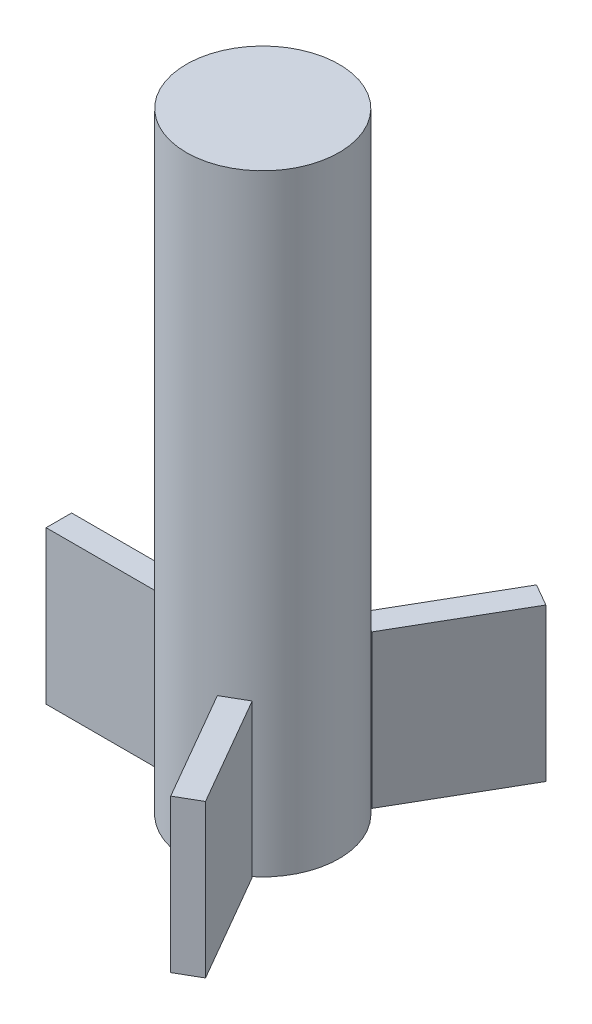
SolidWorks part; units mm, degrees
ref_plane "Alzado" through (0, 0, 0) normal (0, 0, 1) x (1, 0, 0)
ref_plane "Planta" through (0, 0, 0) normal (0, 1, 0) x (1, 0, 0)
ref_plane "Vista lateral" through (0, 0, 0) normal (1, 0, 0) x (0, 0, -1)
sketch "Croquis3" plane through (0, 0, 0) normal (0, 1, 0) x (1, 0, 0)
  line L0 (0, 0.7) -> (0, 13618.4959) construction
  line L1 (-0.6667, 0) -> (-15, 0) construction
  line L2 (-15, 2.5) -> (-40, 2.5)
  line L4 (-15, 2.5) -> (-15, -2.5)
  line L5 (-15, -2.5) -> (-40, -2.5)
  line L6 (-40, 2.5) -> (-40, -2.5)
  line L7 (9.6651, 11.7404) -> (22.1651, 33.391)
  line L8 (22.1651, 33.391) -> (17.8349, 35.891)
  line L9 (5.3349, 14.2404) -> (17.8349, 35.891)
  line L10 (9.6651, 11.7404) -> (5.3349, 14.2404)
  line L11 (5.3349, -14.2404) -> (17.8349, -35.891)
  line L12 (17.8349, -35.891) -> (22.1651, -33.391)
  line L13 (9.6651, -11.7404) -> (22.1651, -33.391)
  line L14 (5.3349, -14.2404) -> (9.6651, -11.7404)
  line L15 (-40, 0) -> (-13618.4626, 0) construction
  circle A0 centre (0, 0) radius 15
  point P23 (0, 0)
  dimension "D1" = 2.5
  dimension "D2" = 25
  dimension "D4" = 15
  dimension "D3" = 3
extrude "Saliente-Extruir1" add sketch "Croquis3" along normal blind 120 contours A0
extrude "Saliente-Extruir2" add sketch "Croquis3<3>" along normal blind 30 separate body contours L12 L13 L14 L11
sketch "Croquis3<3>" plane through (0, 0, 0) normal (0, 1, 0) x (1, 0, 0) same geometry as "Croquis3"
extrude "Saliente-Extruir3" add sketch "Croquis3<4>" along normal blind 30 separate body contours L5 L6 L2 L4
sketch "Croquis3<4>" plane through (0, 0, 0) normal (0, 1, 0) x (1, 0, 0) same geometry as "Croquis3"
extrude "Saliente-Extruir4" add sketch "Croquis3<5>" along normal blind 30 separate body contours L7 L8 L9 L10
sketch "Croquis3<5>" plane through (0, 0, 0) normal (0, 1, 0) x (1, 0, 0) same geometry as "Croquis3"
